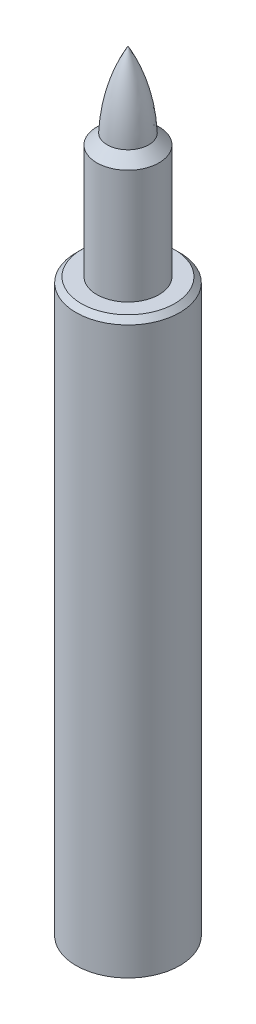
SolidWorks part; units mm, degrees
ref_plane "Front Plane" through (0, 0, 0) normal (0, 0, 1) x (1, 0, 0)
ref_plane "Top Plane" through (0, 0, 0) normal (0, 1, 0) x (1, 0, 0)
ref_plane "Right Plane" through (0, 0, 0) normal (1, 0, 0) x (0, 0, -1)
sketch "Sketch1" plane through (0, 0, 0) normal (0, 1, 0) x (1, 0, 0)
  circle A0 centre (0, 0) radius 10
  dimension "D1" = 20
extrude "Boss-Extrude1" add sketch "Sketch1" along normal blind 110
sketch "Sketch2" plane through (0, 110, 0) normal (0, 1, 0) x (1, 0, 0)
  circle A0 centre (0, 0) radius 6
extrude "Boss-Extrude2" add sketch "Sketch2" along normal blind 24
sketch "Sketch3" plane through (0, 0, 0) normal (1, 0, 0) x (0, 0, -1)
  line L0 (6, 134) -> (-6, 134) construction
  line L1 (0, 134) -> (0, 148.5)
  line L2 (-4, 134) -> (0, 134)
  spline S0 degree 2 poles (0, 148.5) (-3.6674, 141.8675) (-4, 134) knots 0 0 0 1 1 1
  point P0 (0, 134)
  point P6 (-6, 134)
  dimension "D1" = 14.5
  dimension "D2" = 4
ref_axis "Axis1" through (0, 134, 0) along (0, -1, 0)
revolve "Revolve1" add sketch "Sketch3" angle 360 about axis through (0, 134, 0) along (0, -1, 0)
chamfer "Chamfer1" distance 2 angle 45 1 edges at (0, 134, 6)
chamfer "Chamfer2" distance 1 angle 45 1 edges at (0, 110, 10)
